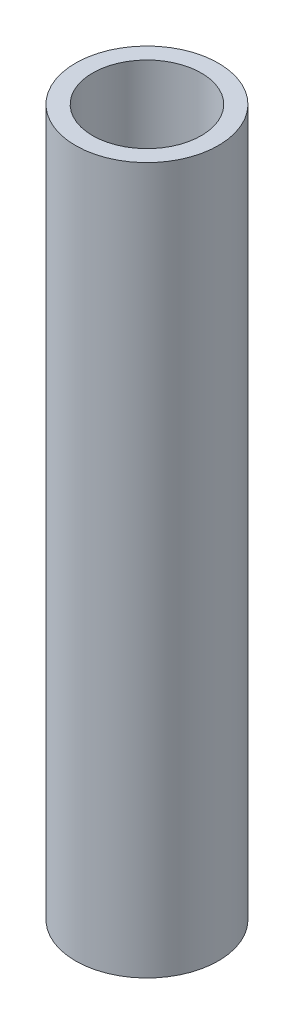
SolidWorks part; units mm, degrees
material "PVC 0.007 Plasticized"
ref_plane "Front Plane" through (0, 0, 0) normal (0, 0, 1) x (1, 0, 0)
ref_plane "Top Plane" through (0, 0, 0) normal (0, 1, 0) x (1, 0, 0)
ref_plane "Right Plane" through (0, 0, 0) normal (1, 0, 0) x (0, 0, -1)
sketch "Sketch1" plane through (0, 0, 0) normal (0, 1, 0) x (1, 0, 0)
  circle A0 centre (0, 0) radius 12.7
  circle A1 centre (0, 0) radius 16.7005
  dimension "D1" = 25.4
  dimension "D2" = 33.401
extrude "Boss-Extrude1" add sketch "Sketch1" along normal blind 165.1 contours A1 A0 region at (-16.2281, 0, 0)
